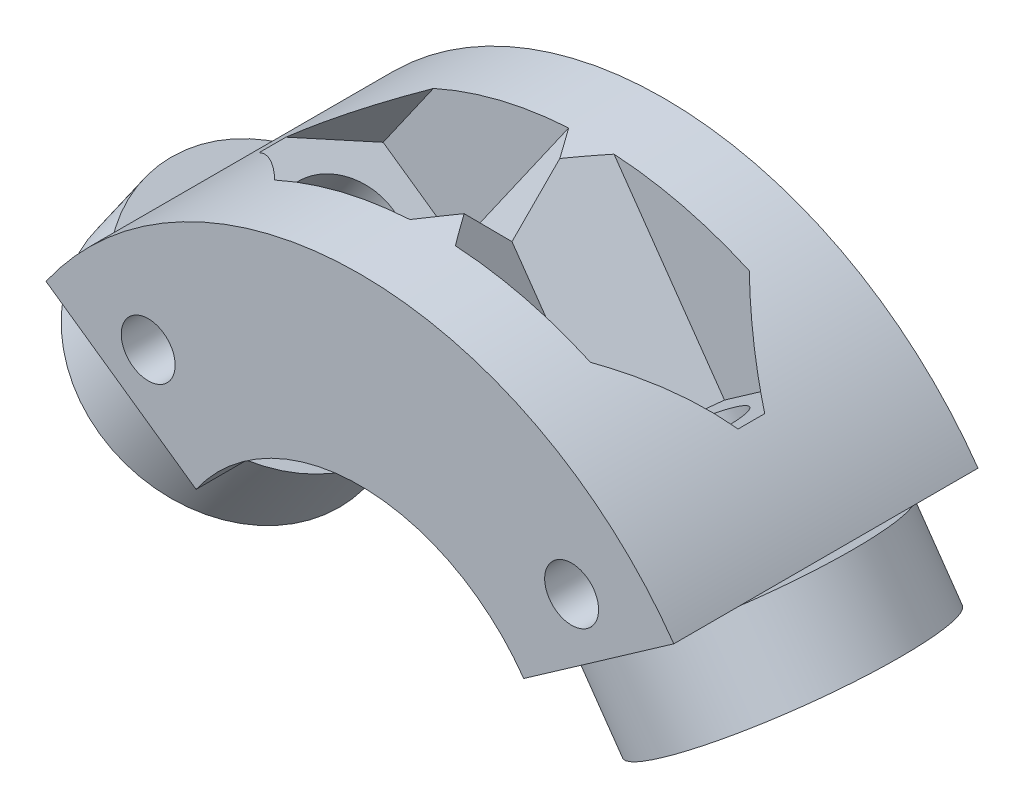
SolidWorks part; units mm, degrees
ref_plane "Front Plane" through (0, 0, 0) normal (0, 0, 1) x (1, 0, 0)
ref_plane "Top Plane" through (0, 0, 0) normal (0, 1, 0) x (1, 0, 0)
ref_plane "Right Plane" through (0, 0, 0) normal (1, 0, 0) x (0, 0, -1)
sketch "Sketch4" plane through (0, 0, 0) normal (0, 0, 1) x (1, 0, 0)
  circle A0 centre (0, 0) radius 12.7 construction
  circle A1 centre (0, 0) radius 23.7 construction
  dimension "D1" = 25.4
  dimension "D2" = 47.4
sketch "Sketch1" plane through (0, 0, 0) normal (0, 0, 1) x (1, 0, 0)
  line L0 (0, 0) -> (26.2129, 18.3544) construction
  line L1 (0, 0) -> (-26.2129, 18.3544) construction
  line L2 (0, 0) -> (0, 32) construction
  line L3 (13.6798, 9.5787) -> (26.2129, 18.3544)
  line L4 (-26.2129, 18.3544) -> (-13.6798, 9.5787)
  line L5 (17.6777, 17.6777) -> (0, 0) construction
  line L6 (0, 0) -> (-17.6777, 17.6777) construction
  arc A0 (-13.6798, 9.5787) -> (13.6798, 9.5787) centre (0, 0) cw
  arc A1 (-26.2129, 18.3544) -> (26.2129, 18.3544) centre (0, 0) cw
  circle A2 centre (-17.6777, 17.6777) radius 2.25
  circle A3 centre (17.6777, 17.6777) radius 2.25
  circle A4 centre (0, 0) radius 23.7 construction
  dimension "D1" = 55
  dimension "D2" = 55
  dimension "D8" = 4.5
  dimension "D3" = 32
  dimension "D4" = 7
  dimension "D5" = 45
  dimension "D6" = 45
  dimension "D7" = 25
extrude "Boss-Extrude1" add sketch "Sketch1" along normal mid plane 25.4 contours A2 | A1 L4 A0 L3 A3 A2 | A3 region at (0, 21.6387, 0) region at (-17.6777, 17.6777, 0) region at (17.6777, 17.6777, 0)
sketch "Sketch3" plane through (0, 0, 0) normal (0.5736, -0.8192, 0) x (0.8192, 0.5736, 0)
  line L0 (16.7, 12.7) -> (16.7, -12.7) construction
  line L2 (19.8751, -6.625) -> (27.5249, -6.625)
  line L3 (27.5249, -6.625) -> (31.3499, 0)
  line L4 (31.3499, 0) -> (27.5249, 6.625)
  line L5 (27.5249, 6.625) -> (19.8751, 6.625)
  line L6 (19.8751, 6.625) -> (16.0501, 0)
  line L7 (16.0501, 0) -> (19.8751, -6.625)
  line L8 (16.0501, 0) -> (31.3499, 0) construction
  line L9 (19.8751, 6.625) -> (27.5249, -6.625) construction
  line L10 (19.8751, -6.625) -> (27.5249, 6.625) construction
  line L11 (23.7, 0) -> (-23.7, 0) construction
  circle A0 centre (23.7, 0) radius 4.35
  point P2 (23.7, 0)
  dimension "D1" = 8.7
  dimension "D2" = 13.25
  dimension "D3" = 7
extrude "Cut-Extrude1" cut sketch "Sketch3" against normal through all both and the other way through all contours A0 region at (19.4139, 13.5938, 0)
extrude "Cut-Extrude2" cut sketch "Sketch1<3>" against normal blind 8 from surface contours A3 region at (17.6777, 17.6777, 0) starting at face at (0, 19.1583, 12.7)
sketch "Sketch1<3>" plane through (0, 0, 0) normal (0, 0, 1) x (1, 0, 0) same geometry as "Sketch1"
extrude "Cut-Extrude4" cut sketch "Sketch1<5>" along normal blind 8 from surface contours A3 region at (17.6777, 17.6777, 0) starting at face at (0, 19.1583, -12.7)
sketch "Sketch1<5>" plane through (0, 0, 0) normal (0, 0, 1) x (1, 0, 0) same geometry as "Sketch1"
extrude "Cut-Extrude3" cut sketch "Sketch3<3>" against normal through all from offset 9 offset against normal yes
sketch "Sketch3<3>" plane through (0, 0, 0) normal (0.5736, -0.8192, 0) x (0.8192, 0.5736, 0) same geometry as "Sketch3"
sketch "Sketch5" plane through (0, 0, 0) normal (0.5736, -0.8192, 0) x (0.8192, 0.5736, 0)
  circle A0 centre (23.7, 0) radius 11
  dimension "D1" = 22
extrude "Boss-Extrude2" add sketch "Sketch5" along normal blind 7
mirror "Mirror1" about plane through (0, 0, 0) normal (1, 0, 0) of "Boss-Extrude2", "Cut-Extrude2", "Cut-Extrude3", "Cut-Extrude1", "Cut-Extrude4"
